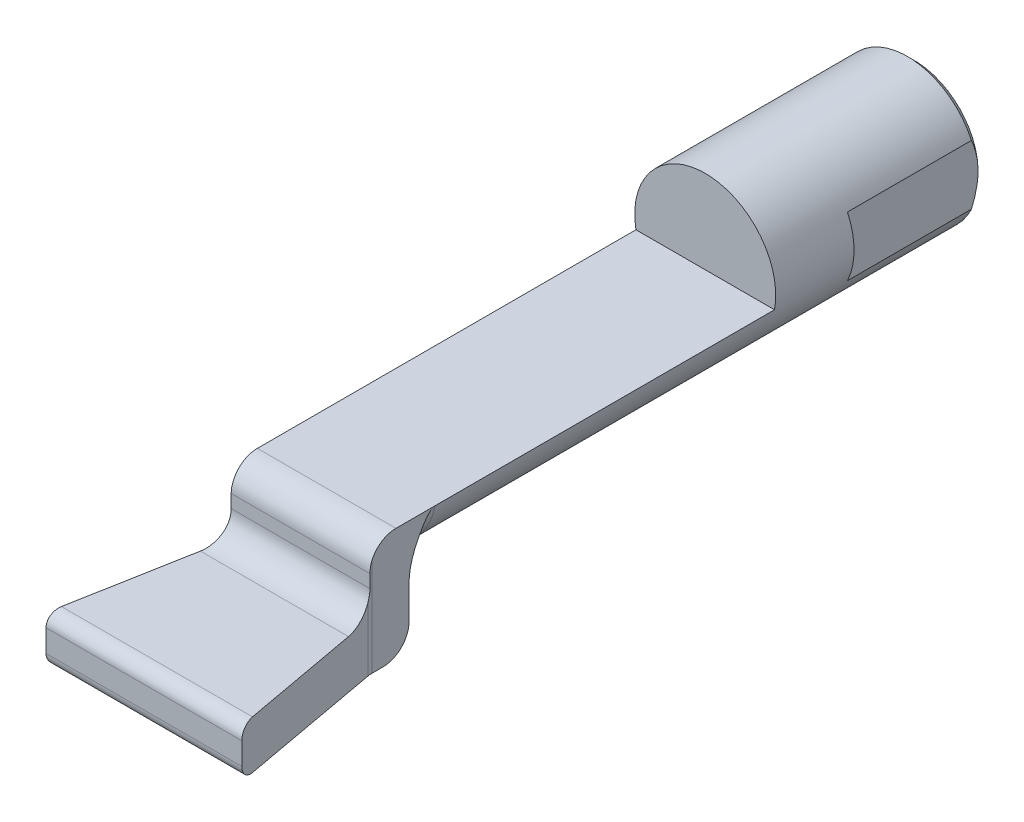
SolidWorks part; units mm, degrees
material "6061 合金"
ref_plane "前视基准面" through (0, 0, 0) normal (0, 0, 1) x (1, 0, 0)
ref_plane "上视基准面" through (0, 0, 0) normal (0, 1, 0) x (1, 0, 0)
ref_plane "右视基准面" through (0, 0, 0) normal (1, 0, 0) x (0, 0, -1)
sketch "草图1" plane through (0, 0, 0) normal (0, 0, 1) x (1, 0, 0)
  circle A0 centre (0, 0) radius 5.4
  dimension "D1" = 10.8
extrude "凸台-拉伸1" add sketch "草图1" along normal blind 44
sketch "草图2" plane through (0, 0, 44) normal (0, 0, 1) x (1, 0, 0)
  line L0 (-5.3066, -1) -> (5.3066, -1)
  arc A0 (5.3066, -1) -> (-5.3066, -1) centre (0, 0) ccw
  circle A1 centre (0, 0) radius 5.4 construction
  dimension "D1" = 1
extrude "切除-拉伸1" cut sketch "草图2" against normal blind 28
sketch "草图3" plane through (0, 0, 44) normal (0, 0, 1) x (1, 0, 0)
  circle A0 centre (-3, -2.5) radius 1
  circle A1 centre (3, -2.5) radius 1
  dimension "D1" = 2
  dimension "D2" = 6
  dimension "D3" = 3
  dimension "D4" = 2.5
extrude "切除-拉伸2" [suppressed] cut sketch "草图3" against normal blind 10
sketch "草图4" plane through (0, 0, 0) normal (0, 0, -1) x (-1, 0, 0)
  line L1 (-5.8955, -2.7209) -> (-4.8955, -2.7209)
  line L2 (-5.8955, -2.7209) -> (-5.8955, 2.2791)
  line L3 (-5.8955, 2.2791) -> (-4.8955, 2.2791)
  line L4 (-4.8955, -2.7209) -> (-4.8955, 2.2791)
  line L5 (-5.8955, -2.7209) -> (-4.8955, 2.2791) construction
  line L6 (-5.8955, 2.2791) -> (-4.8955, -2.7209) construction
  circle A0 centre (0, 0) radius 5.4 construction
  point P0 (-5.3955, -0.2209)
  dimension "D1" = 1
  dimension "D2" = 5
extrude "切除-拉伸3" cut sketch "草图4" against normal blind 10
mirror "镜向1" about plane through (0, 0, 0) normal (1, 0, 0) of "切除-拉伸3"
hole_wizard "M6 螺纹孔1" positions "草图6" profile "草图5" tap size "M6" standard "IS"
sketch "草图6" plane through (0, 0, 0) normal (0, 0, -1) x (-1, 0, 0)
  point P0 (0, 0)
cosmetic thread "孔螺蚊线1" parameters "D2"=6
sketch "草图5" plane through (0, 0, 0) normal (1, 0, 0) x (0, 1, 0)
  line L0 (0, 0) -> (0, 14.5022)
  line L1 (0, 14.5022) -> (2.5, 13)
  line L2 (2.5, 13) -> (2.5, 0)
  line L5 (2.5, 0) -> (0, 0)
  line L10 (0, 14.5022) -> (-2.5, 13) construction
  line L11 (0, -6.35) -> (0, 107.95) construction
  dimension "螺纹孔钻头直径" = 5
  dimension "螺纹孔钻头深度" = 13
  dimension "导头角度" = 118
chamfer "倒角1" distance 0.5 angle 45 3 edges at (-2.5, 0, 0) (0, -5.4, 0) (0, 5.4, 0)
chamfer "倒角2" [suppressed] distance 0.2 angle 45
sketch "草图7" plane through (0, 0, 44) normal (0, 0, 1) x (1, 0, 0)
  line L0 (-5.3066, -1) -> (-5.3066, -10)
  line L1 (-5.3066, -1) -> (5.3066, -1)
  line L2 (5.3066, -1) -> (5.3066, -10)
  line L3 (-5.3066, -10) -> (5.3066, -10)
  point P5 (0, -10)
  point P7 (0, -1)
  dimension "D2" = 10
  dimension "D3" = 10.6132
extrude "凸台-拉伸2" add sketch "草图7" along normal blind 3
sketch "草图9" plane through (0, -10, 0) normal (0, -1, 0) x (1, 0, 0)
  line L0 (5.3066, 47) -> (-5.3066, 47)
  line L1 (-5.3066, 47) -> (-7.5, 59)
  line L2 (-7.5, 59) -> (7.5, 59)
  line L3 (7.5, 59) -> (5.3066, 47)
  point P5 (0, 47)
  point P7 (0, 59)
  dimension "D1" = 12
  dimension "D2" = 15
extrude "凸台-拉伸4" add sketch "草图9" against normal blind 4
fillet "圆角1" radius 2 3 edges at (0, -5.4, 44) (0, -1, 47) (0, -6, 47)
fillet "圆角2" radius 2 2 edges at (-5.3066, -7, 47) (5.3066, -7, 47)
sketch "草图10" plane through (0, -10, 0) normal (0, -1, 0) x (1, 0, 0)
  line L1 (11.663, 59.5107) -> (-11.1698, 59.5107)
  line L2 (11.663, 59.5107) -> (11.663, 42.1396)
  line L3 (11.663, 42.1396) -> (-11.1698, 42.1396)
  line L4 (-11.1698, 59.5107) -> (-11.1698, 42.1396)
extrude "切除-拉伸4" cut sketch "草图10" against normal blind 0.3
fillet "圆角3" radius 2 1 edges at (0, -9.7, 44)
fillet "圆角4" radius 1 1 edges at (0, -6, 59)
fillet "圆角5" radius 1 1 edges at (0, -9.7, 59)
